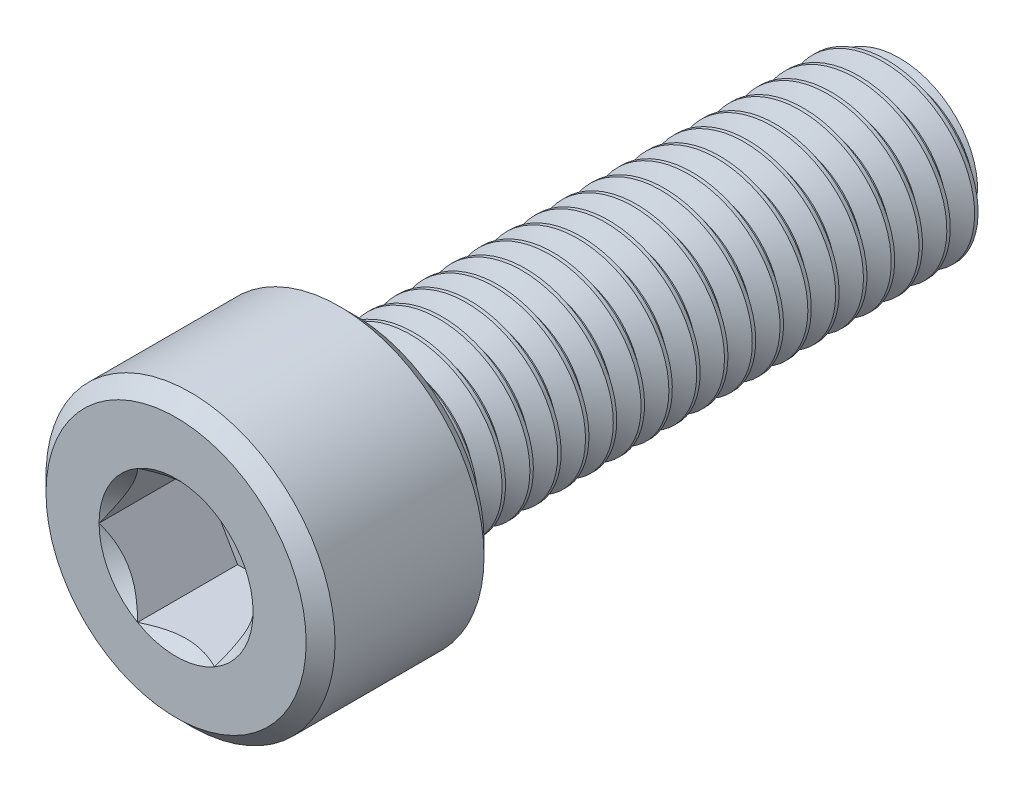
SolidWorks part; units mm, degrees
ref_plane "Front Plane" through (0, 0, 0) normal (0, 0, 1) x (1, 0, 0)
ref_plane "Top Plane" through (0, 0, 0) normal (0, 1, 0) x (1, 0, 0)
ref_plane "Right Plane" through (0, 0, 0) normal (1, 0, 0) x (0, 0, -1)
sketch "Sketch1" plane through (0, 0, 0) normal (0, 0, 1) x (1, 0, 0)
  circle A0 centre (0, 0) radius 4
  dimension "BODY DIAMETER" = 8
extrude "Boss-Extrude1" add sketch "Sketch1" along normal blind 25
sketch "Sketch2" plane through (0, 0, 0) normal (0, 0, -1) x (-1, 0, 0)
  circle A1 centre (0, 0) radius 4
  circle A2 centre (0, 0) radius 4
  dimension "D1" = 0
curve "Helix/Spiral1" pitch 1.25 height 45 turns 36 parameters "PITCH"=1.25
ref_plane "Plane1" through (0, 4, 0) normal (-0.9988, 0, 0.0497) x (0.0497, 0, 0.9988)
sketch "Sketch3" plane through (0, 4, 0) normal (-0.9988, 0, 0.0497) x (0.0497, 0, 0.9988)
  line L0 (0, 0) -> (-1.094, 0)
  line L1 (-1.094, 0) -> (-0.625, -0.8123)
  line L2 (-0.625, -0.8123) -> (-0.469, -0.8123)
  line L3 (-0.469, -0.8123) -> (0, 0)
  line L4 (-0.547, -0.8123) -> (-0.547, 0) construction
  line L5 (-0.8595, -0.4062) -> (-0.2345, -0.4062) construction
  dimension "D1" = 60
  dimension "THREAD DIM1" = 0.156
  dimension "THREAD DIM 2" = 0.625
sweep "Cut-Sweep1" cut profiles "Sketch3" path "Helix/Spiral1" align with end faces yes
sketch "Sketch4" plane through (0, 0, 0) normal (1, 0, 0) x (0, 0, -1)
  line L0 (0, 5) -> (-1.4469, 5)
  line L1 (-1.4469, 5) -> (0, 2.9337)
  line L2 (0, 2.9337) -> (0, 5)
  line L3 (0, 4) -> (1.0926, 4) construction
  line L4 (0, 0) -> (1.7976, 0) construction
  dimension "D1" = 55
  dimension "D2" = 1
  dimension "D3" = 0.254
revolve "Cut-Revolve1" cut sketch "Sketch4" angle 360 about L4
sketch "Sketch5" plane through (0, 0, 25) normal (0, 0, 1) x (1, 0, 0)
  circle A0 centre (0, 0) radius 6.5
  dimension "HEAD DIAMETER" = 13
extrude "Boss-Extrude2" add sketch "Sketch5" along normal blind 8
sketch "Sketch6" plane through (0, 0, 33) normal (0, 0, 1) x (1, 0, 0)
  line L1 (1.7321, 3) -> (-1.7321, 3)
  line L2 (-1.7321, 3) -> (-3.4641, 0)
  line L3 (-3.4641, 0) -> (-1.7321, -3)
  line L4 (-1.7321, -3) -> (1.7321, -3)
  line L5 (1.7321, -3) -> (3.4641, 0)
  line L6 (3.4641, 0) -> (1.7321, 3)
  circle A0 centre (0, 0) radius 3 construction
  dimension "HEX SOCKET SIZE" = 6
extrude "Cut-Extrude1" cut sketch "Sketch6" against normal blind 4.5
sketch "Sketch7" plane through (0, 0, 33) normal (0, 0, 1) x (1, 0, 0)
  circle A0 centre (0, 0) radius 3.4641
extrude "Cut-Extrude2" cut sketch "Sketch7" against normal through all draft 45
chamfer "Chamfer1" distance 0.65 angle 45 2 edges at (6.5, 0, 25) (6.5, 0, 33)
